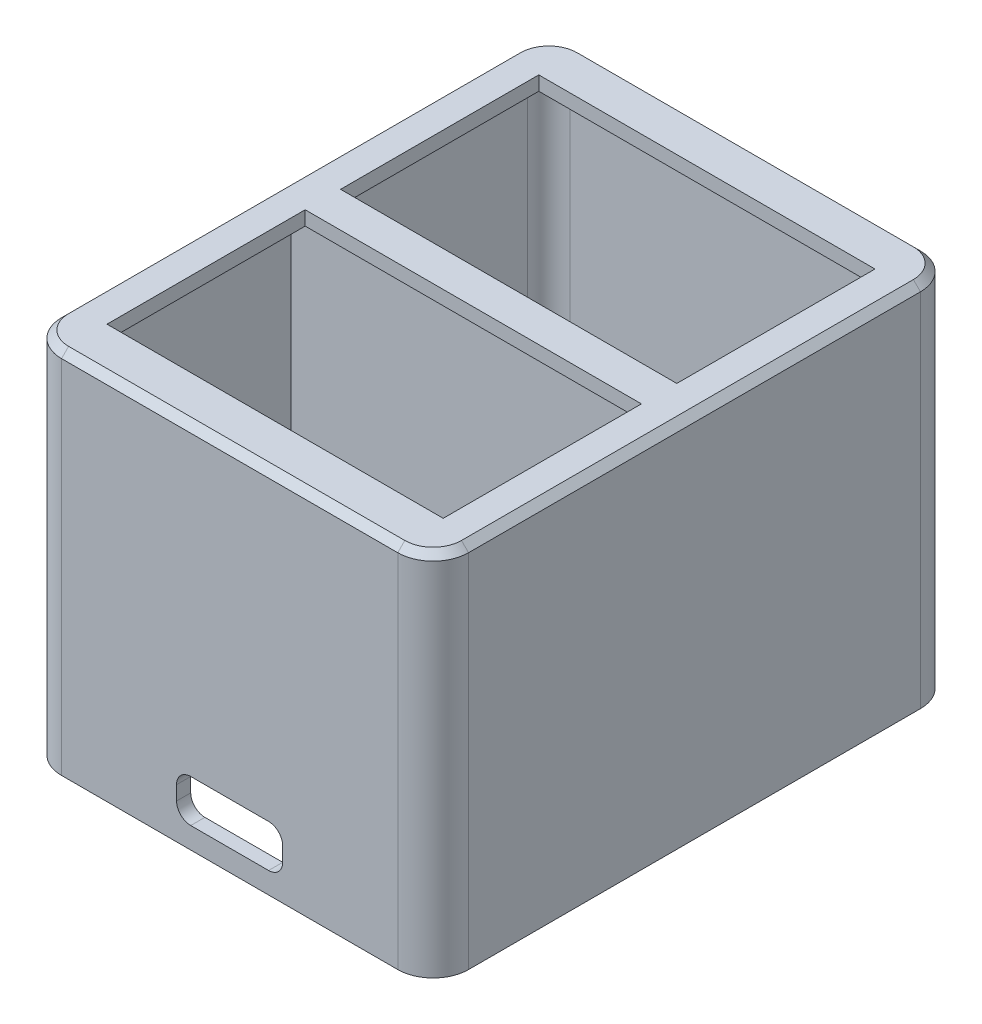
SolidWorks part; units mm, degrees
ref_plane "Front Plane" through (0, 0, 0) normal (0, 0, 1) x (1, 0, 0)
ref_plane "Top Plane" through (0, 0, 0) normal (0, 1, 0) x (1, 0, 0)
ref_plane "Right Plane" through (0, 0, 0) normal (1, 0, 0) x (0, 0, -1)
sketch "Sketch2" plane through (0, 0, 0) normal (0, 1, 0) x (1, 0, 0)
  line L1 (-28.75, 36.9211) -> (28.75, 36.9211)
  line L2 (-28.75, 36.9211) -> (-28.75, -36.9211)
  line L3 (-28.75, -36.9211) -> (28.75, -36.9211)
  line L4 (28.75, 36.9211) -> (28.75, -36.9211)
  line L5 (-28.75, 36.9211) -> (28.75, -36.9211) construction
  line L6 (-28.75, -36.9211) -> (28.75, 36.9211) construction
  line L7 (-23.75, -2.5) -> (23.75, -2.5)
  line L8 (-23.75, -2.5) -> (-23.75, -30.5)
  line L9 (-23.75, -30.5) -> (23.75, -30.5)
  line L10 (23.75, -2.5) -> (23.75, -30.5)
  line L11 (-23.75, 30.5) -> (23.75, 30.5)
  line L12 (-23.75, 30.5) -> (-23.75, 2.5)
  line L13 (-23.75, 2.5) -> (23.75, 2.5)
  line L14 (23.75, 30.5) -> (23.75, 2.5)
  point P0 (0, 0)
  point P5 (0, 0)
  point P15 (25.163, 25.163)
  point P16 (28.75, -37.2884)
  dimension "D1" = 5
  dimension "D2" = 47.5
  dimension "D3" = 28
  dimension "D4" = 5
extrude "Boss-Extrude1" add sketch "Sketch2" along normal blind 2
sketch "Sketch3" plane through (0, 0, 0) normal (0, -1, 0) x (1, 0, 0)
  line L0 (-26.75, -1.5) -> (-26.75, -34.9211)
  line L1 (-26.75, 1.5) -> (26.75, 1.5)
  line L3 (-26.75, -1.5) -> (26.75, -1.5)
  line L5 (-26.75, 1.5) -> (26.75, -1.5) construction
  line L6 (-26.75, -1.5) -> (26.75, 1.5) construction
  line L7 (26.75, 1.5) -> (26.75, 34.9211)
  line L8 (26.75, -34.9211) -> (26.75, 34.9211)
  line L9 (26.75, 34.9211) -> (-26.75, 34.9211)
  line L10 (-26.75, 34.9211) -> (-26.75, -34.9211)
  line L11 (-26.75, -34.9211) -> (26.75, -34.9211)
  line L12 (26.75, -34.9211) -> (26.75, -1.5)
  line L13 (26.75, 34.9211) -> (-26.75, 34.9211)
  line L14 (-26.75, 34.9211) -> (-26.75, 1.5)
  line L15 (-26.75, -34.9211) -> (26.75, -34.9211)
  line L16 (28.75, -36.9211) -> (28.75, 36.9211)
  line L17 (28.75, 36.9211) -> (-28.75, 36.9211)
  line L18 (-28.75, 36.9211) -> (-28.75, -36.9211)
  line L19 (-28.75, -36.9211) -> (28.75, -36.9211)
  line L20 (28.75, -36.9211) -> (28.75, 36.9211)
  line L21 (28.75, 36.9211) -> (-28.75, 36.9211)
  line L22 (-28.75, 36.9211) -> (-28.75, -36.9211)
  line L23 (-28.75, -36.9211) -> (28.75, -36.9211)
  point P2 (0, 0)
  dimension "D3" = 3
  dimension "D1" = 2
  dimension "D2" = 0
extrude "Boss-Extrude2" add sketch "Sketch3" along normal blind 50
fillet "Fillet1" radius 3 4 edges at (-26.75, -25, 34.9211) (26.75, -25, -34.9211) (-26.75, -25, -34.9211) (26.75, -25, 34.9211)
fillet "Fillet2" radius 5 4 edges at (-28.75, -24, 36.9211) (-28.75, -24, -36.9211) (28.75, -24, -36.9211) (28.75, -24, 36.9211)
sketch "Sketch4" plane through (0, 0, 36.9211) normal (0, 0, 1) x (1, 0, 0)
  line L0 (-7.5, -47) -> (-7.5, -41)
  line L2 (-7.5, -41) -> (7.5, -41)
  line L3 (7.5, -41) -> (7.5, -47)
  line L4 (7.5, -47) -> (-7.5, -47)
  line L5 (23.75, -50) -> (-23.75, -50) construction
  point P2 (7.5, -43.007)
  point P4 (0, -41)
  point P7 (0, 0)
  dimension "D1" = 6
  dimension "D2" = 15
  dimension "D3" = 3
extrude "Cut-Extrude1" cut sketch "Sketch4" against normal blind 4
mirror "Mirror2" about plane through (0, 0, 0) normal (0, 0, 1) of "Cut-Extrude1"
fillet "Fillet3" radius 2 8 edges at (7.5, -41, 35.9211) (-7.5, -41, 35.9211) (7.5, -41, -35.9211) (-7.5, -41, -35.9211) (7.5, -47, 35.9211) (-7.5, -47, 35.9211) (-7.5, -47, -35.9211) (7.5, -47, -35.9211)
chamfer "Chamfer1" distance 1 angle 45 8 edges at (-27.2855, 2, -35.4566) (-28.75, 2, 0) (0, 2, -36.9211) (-27.2855, 2, 35.4566) (27.2855, 2, -35.4566) (0, 2, 36.9211) (28.75, 2, 0) (27.2855, 2, 35.4566)
sketch "Sketch6" plane through (0, -50, 0) normal (0, -1, 0) x (1, 0, 0)
  line L0 (-28.75, 31.9211) -> (-28.75, -31.9211) construction
  line L1 (-28.75, 20.5) -> (-13.75, 20.5)
  line L2 (-28.75, 20.5) -> (-28.75, 12.5)
  line L3 (-28.75, 12.5) -> (-13.75, 12.5)
  line L4 (-13.75, 20.5) -> (-13.75, 12.5)
  line L5 (-13.75, 16.5) -> (-28.75, 16.5) construction
  line L7 (-23.75, 2.5) -> (-23.75, 30.5) construction
  line L8 (-23.75, 16.5) -> (23.75, 16.5) construction
  line L9 (23.75, 30.5) -> (23.75, 2.5) construction
  line L10 (-28.75, 20.5) -> (-13.75, 20.5)
  line L11 (-28.75, 12.5) -> (-13.75, 12.5)
  line L12 (0, -28.6) -> (0, 28.6) construction
  line L14 (28.75, 12.5) -> (13.75, 12.5)
  line L15 (28.75, 20.5) -> (13.75, 20.5)
  line L16 (13.75, 20.5) -> (13.75, 12.5)
  line L17 (28.75, 12.5) -> (13.75, 12.5)
  line L18 (28.75, 20.5) -> (28.75, 12.5)
  line L19 (28.75, 20.5) -> (13.75, 20.5)
  circle A0 centre (-18.75, 16.5) radius 1.75
  circle A1 centre (18.75, 16.5) radius 1.75
  point P6 (-13.75, 16.5)
  line M11 (-26.75, 1.5) -> (-26.75, 31.9211)
  line M26 (26.75, 31.9211) -> (26.75, 1.5)
  dimension "D3" = 5
  dimension "D4" = 3.5
  dimension "D1" = 15
  dimension "D2" = 8
extrude "Boss-Extrude3" add sketch "Sketch6" against normal blind 2.5 contours L4 L1 L3 A0 M11 | L15 L16 L14 A1 M26 region at (-20.25, -50, 20.3474) region at (20.25, -50, 12.6526)
mirror "Mirror1" about plane through (0, 0, 0) normal (0, 0, 1) of "Boss-Extrude3"
fillet "Fillet4" radius 3 16 edges at (-13.75, -48.75, 12.5) (-26.75, -48.75, 12.5) (-26.75, -48.75, 20.5) (-13.75, -48.75, 20.5) (-13.75, -48.75, -12.5) (-13.75, -48.75, -20.5) (26.75, -48.75, -12.5) (-26.75, -48.75, -20.5) (-26.75, -48.75, -12.5) (26.75, -48.75, -20.5) (13.75, -48.75, -20.5) (13.75, -48.75, -12.5) (26.75, -48.75, 12.5) (26.75, -48.75, 20.5) (13.75, -48.75, 20.5) (13.75, -48.75, 12.5)
